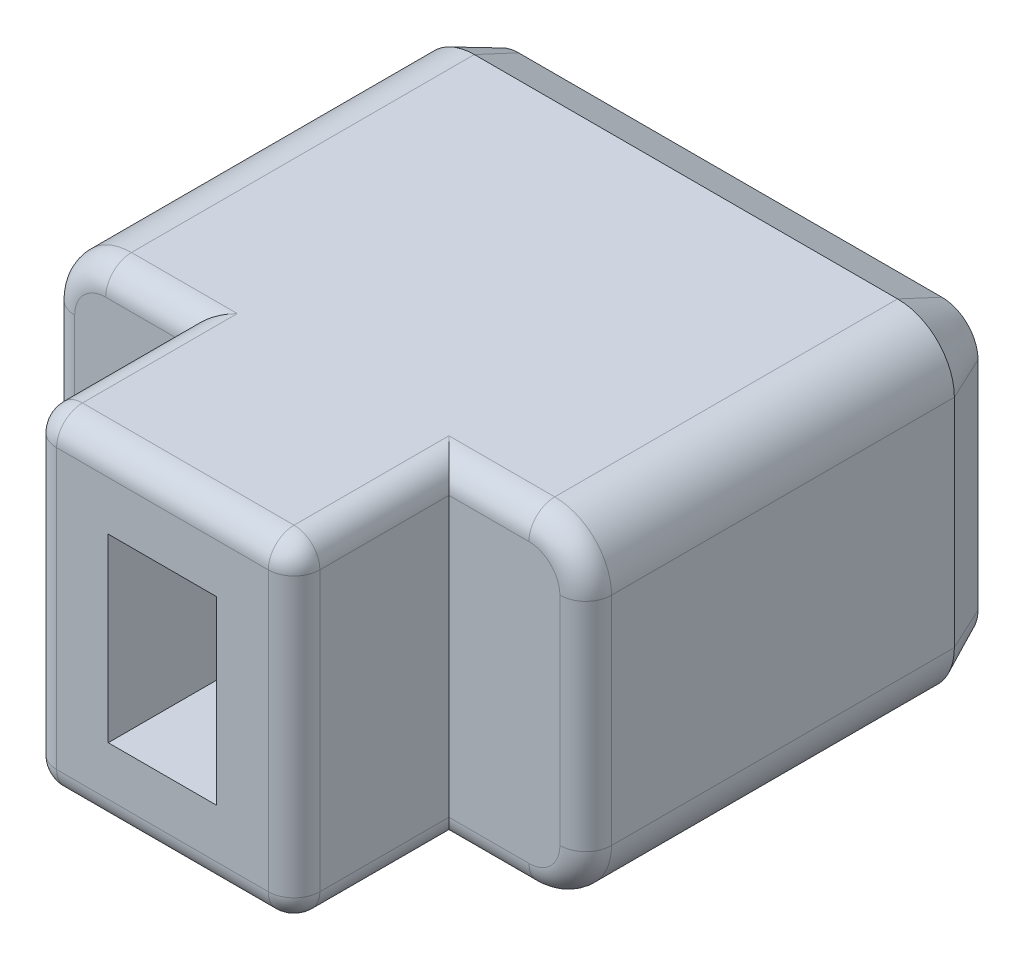
SolidWorks part; units mm, degrees
ref_plane "Plan de face" through (0, 0, 0) normal (0, 0, 1) x (1, 0, 0)
ref_plane "Plan de dessus" through (0, 0, 0) normal (0, 1, 0) x (1, 0, 0)
ref_plane "Plan de droite" through (0, 0, 0) normal (1, 0, 0) x (0, 0, -1)
sketch "Esquisse2" plane through (0, 0, 0) normal (0, 0, 1) x (1, 0, 0)
  line L1 (1.1, 0) -> (9.3, 0)
  line L2 (0, 1.1) -> (0, 5.3)
  line L3 (1.1, 6.4) -> (9.3, 6.4)
  line L4 (10.4, 1.1) -> (10.4, 5.3)
  arc A0 (9.3, 6.4) -> (10.4, 5.3) centre (9.3, 5.3) cw
  arc A1 (9.3, 0) -> (10.4, 1.1) centre (9.3, 1.1) ccw
  arc A2 (1.1, 0) -> (0, 1.1) centre (1.1, 1.1) cw
  arc A3 (0, 5.3) -> (1.1, 6.4) centre (1.1, 5.3) cw
  point P7 (10.4, 6.4)
  point P12 (0, 0)
  point P15 (0, 6.4)
  dimension "D3" = 1.1
  dimension "D1" = 10.4
  dimension "D2" = 6.4
extrude "Boss.-Extru.1" add sketch "Esquisse2" along normal blind 11
sketch "Esquisse3" plane through (0, 0, 11) normal (0, 0, 1) x (1, 0, 0)
  line L0 (0, 5.3) -> (0, 1.1) construction
  line L1 (4.15, 4.95) -> (6.25, 4.95)
  line L2 (4.15, 4.95) -> (4.15, 1.45)
  line L3 (4.15, 1.45) -> (6.25, 1.45)
  line L4 (6.25, 4.95) -> (6.25, 1.45)
  line L5 (10.4, 1.1) -> (10.4, 5.3) construction
  line L6 (9.3, 6.4) -> (1.1, 6.4) construction
  line L7 (1.1, 0) -> (9.3, 0) construction
  dimension "D1" = 2.1
  dimension "D2" = 3.5
  dimension "D3" = 4.15
  dimension "D4" = 4.15
  dimension "D5" = 1.45
  dimension "D6" = 1.45
extrude "Enlèv. mat.-Extru.1" cut sketch "Esquisse3" against normal blind 3
sketch "Esquisse4" plane through (0, 0, 11) normal (0, 0, 1) x (1, 0, 0)
  line L0 (2.65, 6.4) -> (2.65, 0)
  line L1 (9.3, 6.4) -> (1.1, 6.4) construction
  line L2 (1.1, 0) -> (9.3, 0) construction
  line L3 (2.65, 0) -> (7.75, 0)
  line L4 (7.75, 0) -> (7.75, 6.4)
  line L5 (7.75, 6.4) -> (2.65, 6.4)
  line L6 (4.15, 4.95) -> (4.15, 1.45) construction
  line L7 (6.25, 1.45) -> (6.25, 4.95) construction
  dimension "D1" = 1.5
  dimension "D2" = 1.5
extrude "Enlèv. mat.-Extru.2" cut sketch "Esquisse4" against normal blind 3 flip side to cut
fillet "Congé1" radius 0.5 18 edges at (8.525, 0, 8) (10.0778, 0.3222, 8) (10.4, 3.2, 8) (10.0778, 6.0778, 8) (1.875, 6.4, 8) (0.3222, 6.0778, 8) (1.875, 0, 8) (0.3222, 0.3222, 8) (7.75, 6.4, 9.5) (2.65, 6.4, 9.5) (7.75, 0, 9.5) (2.65, 0, 9.5) (2.65, 3.2, 11) (5.2, 6.4, 11) (7.75, 3.2, 11) (5.2, 0, 11) (8.525, 6.4, 8) (0, 3.2, 8)
chamfer "Chanfrein1" distance 0.4 angle 65 8 edges at (5.2, 0, 0) (10.0778, 0.3222, 0) (0.3222, 0.3222, 0) (10.4, 3.2, 0) (0, 3.2, 0) (10.0778, 6.0778, 0) (0.3222, 6.0778, 0) (5.2, 6.4, 0) first distance on face at (5.2, 3.2, 0)
sketch "Esquisse5" plane through (0, 0, 0) normal (0, 0, -1) x (-1, 0, 0)
  line L0 (-0.4, 5.3) -> (-10, 5.3) construction
  arc A0 (-9.3, 6) -> (-10, 5.3) centre (-9.3, 5.3) ccw construction
  text T0 "VFR" font "Century Gothic" height 4
extrude "Enlèv. mat.-Extru.3" cut sketch "Esquisse5" against normal blind 0.3
extrude "Boss.-Extru.2" add sketch "Esquisse5<2>" along normal blind 0.3 separate body
sketch "Esquisse5<2>" plane through (0, 0, 0) normal (0, 0, -1) x (-1, 0, 0) same geometry as "Esquisse5"
